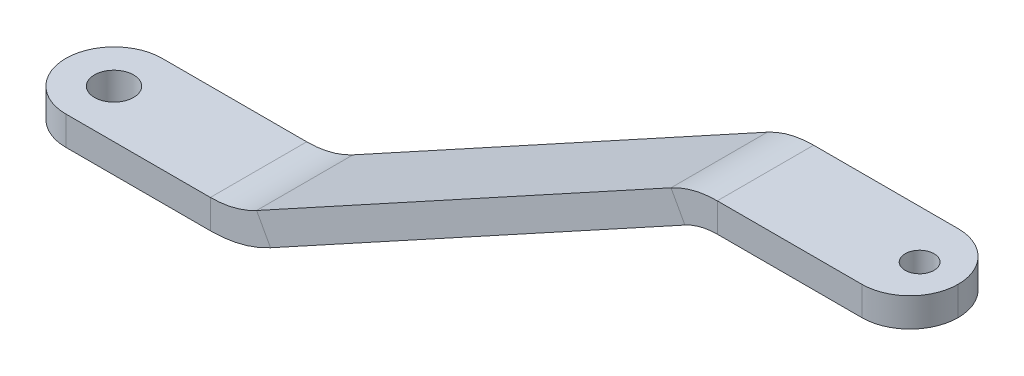
SolidWorks part; units mm, degrees
ref_plane "Front Plane" through (0, 0, 0) normal (0, 0, 1) x (1, 0, 0)
ref_plane "Top Plane" through (0, 0, 0) normal (0, 1, 0) x (1, 0, 0)
ref_plane "Right Plane" through (0, 0, 0) normal (1, 0, 0) x (0, 0, -1)
sketch "Sketch4" plane through (0, 0, 0) normal (0, 0, 1) x (1, 0, 0)
  line L0 (-45.1751, 1.5) -> (-25.1751, 1.5)
  line L1 (-20.3731, 2.7284) -> (22.6328, 26.2716)
  line L2 (27.4347, 27.5) -> (47.4347, 27.5)
  arc A0 (22.6328, 26.2716) -> (27.4347, 27.5) centre (27.4347, 17.5) cw
  arc A1 (-25.1751, 1.5) -> (-20.3731, 2.7284) centre (-25.1751, 11.5) ccw
  dimension "D2" = 10
  dimension "D1" = 26
  dimension "D3" = 20
  dimension "D4" = 20
  dimension "D5" = 92.6098
  dimension "D6" = 45.1751
  dimension "D7" = 1.5
ref_plane "Plane1" through (-45.1751, 0, 0) normal (1, 0, 0) x (0, 0, -1)
sketch "Sketch3" plane through (-45.1751, 0, 0) normal (-1, 0, 0) x (0, 0, 1)
  line L1 (10, 1.5) -> (0, 1.5)
  line L2 (10, 1.5) -> (10, -1.5)
  line L3 (10, -1.5) -> (0, -1.5)
  line L4 (0, 1.5) -> (0, -1.5)
  dimension "D1" = 10
  dimension "D2" = 3
sweep "Sweep1" add profiles "Sketch3" path "Sketch4"
sketch "Sketch5" plane through (0, 27.5, 0) normal (0, 1, 0) x (1, 0, 0)
  line L1 (47.4347, -10) -> (47.4347, 0) construction
  line L2 (27.4347, 0) -> (22.6328, 0) construction
  circle A0 centre (43.4347, -5) radius 1.5
  dimension "D1" = 3
  dimension "D2" = 4
  dimension "D3" = 5
extrude "Cut-Extrude2" cut sketch "Sketch5" against normal through all
sketch "Sketch2" plane through (0, 1.5, 0) normal (0, 1, 0) x (1, 0, 0)
  line L4 (-40.1751, -0.1947) -> (-40.1751, -10.1947) construction
  line L6 (-45.1751, 0) -> (-25.1751, 0) construction
  line L7 (-45.1751, -5.5) -> (-45.1751, 5.5) construction
  circle A0 centre (-40.1751, -5) radius 2.032
  dimension "D1" = 4.064
  dimension "D2" = 5
  dimension "D3" = 5
extrude "Cut-Extrude1" cut sketch "Sketch2" against normal through all
fillet "Fillet1" radius 5 4 edges at (47.4347, 26, 0) (47.4347, 26, 10) (-45.1751, 0, 10) (-45.1751, 0, 0)
